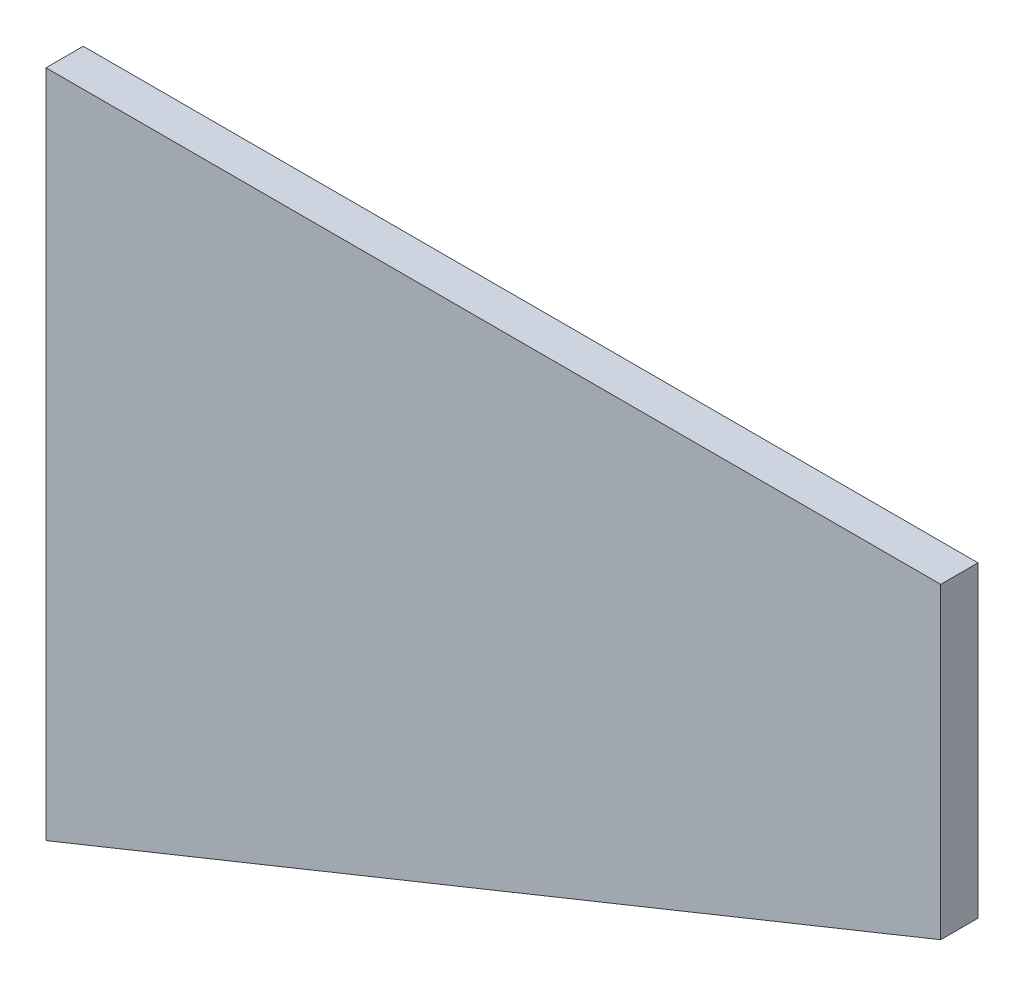
SolidWorks part; units mm, degrees
ref_plane "Front Plane" through (0, 0, 0) normal (0, 0, 1) x (1, 0, 0)
ref_plane "Top Plane" through (0, 0, 0) normal (0, 1, 0) x (1, 0, 0)
ref_plane "Right Plane" through (0, 0, 0) normal (1, 0, 0) x (0, 0, -1)
sketch "Sketch1" plane through (0, 0, 0) normal (0, 0, 1) x (1, 0, 0)
  line L0 (2683.51, 6641.7419) -> (3140.71, 6826.4627) construction
  line L1 (2683.51, 7002.78) -> (2683.51, 5935.98) construction
  line L8 (2683.51, 6983.73) -> (2683.51, 6641.7419)
  line L9 (2683.51, 6641.7419) -> (3140.71, 6826.4627)
  line L10 (3140.71, 6826.4627) -> (3140.71, 6983.73)
  line L11 (3140.71, 6983.73) -> (2683.51, 6983.73)
  point P2 (2683.51, 6983.73)
  point P4 (3140.71, 6983.73)
  point P6 (3140.71, 6983.73)
  point P11 (3140.71, 6983.73)
extrude "Boss-Extrude1" add sketch "Sketch1" along normal blind 19.05
